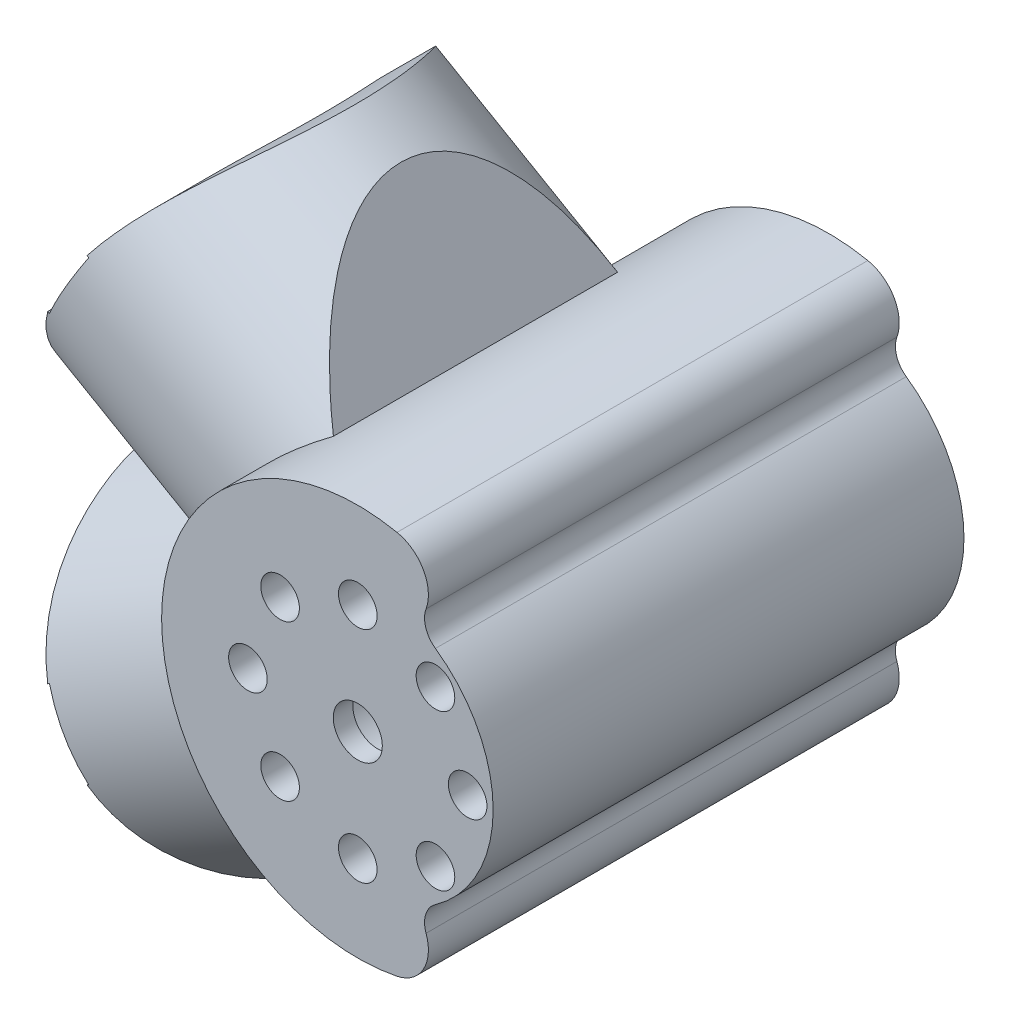
SolidWorks part; units mm, degrees
ref_plane "Front Plane" through (0, 0, 0) normal (0, 0, 1) x (1, 0, 0)
ref_plane "Top Plane" through (0, 0, 0) normal (0, 1, 0) x (1, 0, 0)
ref_plane "Right Plane" through (0, 0, 0) normal (1, 0, 0) x (0, 0, -1)
sketch "Sketch1" plane through (0, 0, 0) normal (0, 1, 0) x (1, 0, 0)
  circle A0 centre (0, 0) radius 11.176
  circle A1 centre (0, 0) radius 8.636
  dimension "D1" = 22.352
  dimension "D2" = 17.272
extrude "Boss-Extrude1" add sketch "Sketch1" along normal blind 20.32
sketch "Sketch2" plane through (0, 0, 0) normal (0, 0, 1) x (1, 0, 0)
  line L0 (11.176, 20.32) -> (-11.176, 20.32) construction
  line L1 (-8.636, 20.32) -> (-11.176, 20.32)
  line L2 (8.4632, 20.32) -> (11.0032, 20.32)
  line L3 (0, 20.32) -> (0, 38.4954) construction
  arc A2 (8.4632, 20.32) -> (-8.636, 20.32) centre (-0.0864, 7.6039) ccw
  arc A3 (11.0032, 20.32) -> (-11.176, 20.32) centre (-0.0864, 7.6039) ccw
revolve "Revolve1" add sketch "Sketch2" angle 360 about L3 region at (-9.906, 20.5457, 0)
ref_plane "Plane1" through (0, 27.94, 0) normal (0, -1, 0) x (-1, 0, 0)
sketch "Sketch3" plane through (0, 27.94, 0) normal (0, -1, 0) x (-1, 0, 0)
  line L0 (0, 11.9871) -> (0, -12.3331)
pattern_circular "CirPattern1" count 6 over 360 about axis through (0, 27.94, -11.9871) along (0, 0, 1) of bodies 103
sketch "Sketch4" plane through (0, 0, 0) normal (0, 0, 1) x (1, 0, 0)
  circle A0 centre (0, 27.94) radius 12.7
  dimension "D1" = 25.4
extrude "Boss-Extrude2" add sketch "Sketch4" along normal blind 13.97 and the other way blind 16.51
sketch "Sketch5" plane through (0, 0, 13.97) normal (0, 0, 1) x (1, 0, 0)
  circle A0 centre (0, 27.94) radius 25.4
  circle A1 centre (0, 27.94) radius 34.3456
  dimension "D1" = 50.8
extrude "Cut-Extrude1" cut sketch "Sketch5" against normal through all
sketch "Sketch8" plane through (0, 0, 0) normal (0, 1, 0) x (1, 0, 0)
  circle A0 centre (0, 0) radius 8.636
extrude "Cut-Extrude2" cut sketch "Sketch8" along normal up to surface (15.24 mm away) up to face at (0.2598, 15.3358, 2.1433)
pattern_circular "CirPattern2" count 6 over 360 about axis through (0, 27.94, -16.51) along (0, 0, 1) of "Cut-Extrude2"
sketch "Sketch9" plane through (0, 0, -16.51) normal (0, 0, -1) x (-1, 0, 0)
  line L0 (-159.3608, -65.013) -> (-26.0275, -65.013) construction
  line L1 (-5.3001, 25.0893) -> (-5.3001, 24.6378)
  line L2 (-5.3001, 32.5511) -> (5.1143, 32.5511)
  line L3 (-6.5701, 31.2811) -> (-6.5701, 23.7722)
  line L4 (-5.3001, 22.5022) -> (5.1143, 22.5022)
  line L5 (6.3843, 31.2811) -> (6.3843, 23.7722)
  line L6 (-4.9342, 31.6555) -> (4.7922, 31.6555)
  line L7 (-5.6962, 30.8935) -> (-5.6962, 24.1162)
  line L8 (-4.9342, 23.3542) -> (4.7922, 23.3542)
  line L9 (5.5542, 30.8935) -> (5.5542, 24.1162)
  line L10 (-5.3001, 24.6378) -> (-3.6843, 24.6378)
  line L11 (-3.6843, 24.6378) -> (-3.6843, 25.0893)
  line L12 (-3.6843, 25.0893) -> (-4.0153, 25.0893)
  line L13 (-4.0153, 25.0893) -> (-2.7662, 29.1074)
  line L14 (-2.7662, 29.1074) -> (-0.7496, 27.3015)
  line L15 (-0.7496, 27.3015) -> (-0.7496, 24.8635)
  line L16 (-0.7496, 24.8635) -> (-1.5021, 24.8635)
  line L17 (-1.5021, 24.8635) -> (-1.5021, 24.4572)
  line L18 (-1.5021, 24.4572) -> (-0.2379, 24.4572)
  line L19 (-0.2379, 24.4572) -> (-0.2379, 31.2811)
  line L20 (-0.2379, 31.2811) -> (-1.7579, 31.2811)
  line L21 (-1.7579, 31.2811) -> (-1.7579, 30.7478)
  line L22 (-1.7579, 30.7478) -> (-0.7496, 30.7478)
  line L23 (-0.7496, 30.7478) -> (-0.7496, 28.656)
  line L24 (-0.7496, 28.656) -> (-2.6007, 30.507)
  line L25 (-2.6007, 30.507) -> (-4.3163, 25.0893)
  line L26 (-4.3163, 25.0893) -> (-5.3001, 25.0893)
  line L27 (-0.071, 31.6555) -> (-0.071, 23.3542) construction
  line L28 (2.4587, 30.507) -> (4.1743, 25.0893)
  line L29 (0.6076, 28.656) -> (2.4587, 30.507)
  line L30 (0.6076, 30.7478) -> (0.6076, 28.656)
  line L31 (1.6159, 30.7478) -> (0.6076, 30.7478)
  line L32 (1.6159, 31.2811) -> (1.6159, 30.7478)
  line L33 (0.0959, 31.2811) -> (1.6159, 31.2811)
  line L34 (0.0959, 24.4572) -> (0.0959, 31.2811)
  line L35 (1.3601, 24.4572) -> (0.0959, 24.4572)
  line L36 (1.3601, 24.8635) -> (1.3601, 24.4572)
  line L37 (0.6076, 24.8635) -> (1.3601, 24.8635)
  line L38 (0.6076, 27.3015) -> (0.6076, 24.8635)
  line L39 (2.6242, 29.1074) -> (0.6076, 27.3015)
  line L40 (3.8733, 25.0893) -> (2.6242, 29.1074)
  line L41 (3.5422, 25.0893) -> (3.8733, 25.0893)
  line L42 (3.5422, 24.6378) -> (3.5422, 25.0893)
  line L43 (5.158, 24.6378) -> (3.5422, 24.6378)
  line L44 (5.158, 25.0893) -> (5.158, 24.6378)
  line L45 (4.1743, 25.0893) -> (5.158, 25.0893)
  line L47 (-5.3001, 24.3067) -> (5.1143, 24.3067)
  line L48 (-5.3001, 24.3067) -> (-5.3001, 23.8703)
  line L49 (-5.3001, 23.8703) -> (5.1143, 23.8703)
  line L50 (5.1143, 24.3067) -> (5.1143, 23.8703)
  arc A0 (5.1143, 32.5511) -> (6.3843, 31.2811) centre (5.1143, 31.2811) cw
  arc A1 (5.1143, 22.5022) -> (6.3843, 23.7722) centre (5.1143, 23.7722) ccw
  arc A2 (-6.5701, 23.7722) -> (-5.3001, 22.5022) centre (-5.3001, 23.7722) ccw
  arc A3 (-5.3001, 32.5511) -> (-6.5701, 31.2811) centre (-5.3001, 31.2811) ccw
  arc A4 (4.7922, 31.6555) -> (5.5542, 30.8935) centre (4.7922, 30.8935) cw
  arc A5 (4.7922, 23.3542) -> (5.5542, 24.1162) centre (4.7922, 24.1162) ccw
  arc A6 (-5.6962, 24.1162) -> (-4.9342, 23.3542) centre (-4.9342, 24.1162) ccw
  arc A7 (-4.9342, 31.6555) -> (-5.6962, 30.8935) centre (-4.9342, 30.8935) ccw
  dimension "D1" = 1.27
  dimension "D2" = 0.762
extrude "Cut-Extrude3" [suppressed] cut sketch "Sketch9" against normal blind 1.27 contours L25 L26 L1 L10 L11 L12 L13 L14 L15 L16 L17 L18 L19 L20 L21 L22 L23 L24 | L45 L28 L29 L30 L31 L32 L33 L34 L35 L36 L37 L38 L39 L40 L41 L42 L43 L44 | L2 A3 L3 A2 L4 A1 L5 A0 A7 L6 A4 L9 A5 L8 A6 L7
sketch "Sketch10" plane through (0, 0, 13.97) normal (0, 0, 1) x (1, 0, 0)
  circle A0 centre (0, 27.94) radius 1.5875
  arc A1 (-6.35, 38.9385) -> (-12.7, 27.94) centre (0, 27.94) ccw construction
  dimension "D1" = 3.175
extrude "Cut-Extrude4" cut sketch "Sketch10" against normal blind 1.27 contours A0
sketch "Sketch12" plane through (0, 0, 0) normal (0, 0, 1) x (1, 0, 0)
  line L1 (-12.7, 27.94) -> (-17.272, 27.94) construction
  arc A2 (-6.35, 38.9385) -> (-12.7, 27.94) centre (0, 27.94) ccw construction
  ellipse E0 centre (-12.7, 27.94) end of major axis (-17.78, 27.94) minor radius 1.27
  dimension "D1" = 10.16
  dimension "D2" = 2.54
extrude "Boss-Extrude3" add sketch "Sketch12" along normal up to next and the other way up to next
pattern_circular "CirPattern3" count 6 over 360 about axis through (0, 27.94, -16.51) along (0, 0, 1) of "Boss-Extrude3"
sketch "Sketch13" plane through (0, 0, -16.51) normal (0, 0, -1) x (-1, 0, 0)
  circle A0 centre (0, 27.94) radius 3.175
  circle A1 centre (0, 27.94) radius 12.7 construction
  dimension "D1" = 6.35
extrude "Cut-Extrude5" cut sketch "Sketch13" against normal up to surface (29.21 mm away) up to face at (1.5875, 27.94, 12.7)
sketch "Sketch14" plane through (0, 0, 13.97) normal (0, 0, 1) x (1, 0, 0)
  line L0 (-7.112, 27.94) -> (7.112, 27.94) construction
  circle A0 centre (-7.112, 27.94) radius 1.25
  point P5 (0, 27.94)
  dimension "D1" = 2.5
  dimension "D2" = 7.112
extrude "Cut-Extrude6" cut sketch "Sketch14" against normal blind 7
pattern_circular "CirPattern4" count 8 over 360 about axis through (0, 27.94, 13.97) along (0, 0, 1) of "Cut-Extrude6"
sketch "Sketch15" plane through (0, 0, 13.97) normal (0, 0, 1) x (1, 0, 0)
  line L1 (-2.54, 56.7733) -> (2.54, 56.7733)
  line L2 (-2.54, 56.7733) -> (-2.54, 53.086)
  line L3 (-2.54, 53.086) -> (2.54, 53.086)
  line L4 (2.54, 56.7733) -> (2.54, 53.086)
  arc A0 (8.636, 51.8268) -> (-8.636, 51.8268) centre (0, 27.94) ccw construction
  point P4 (0, 53.34)
  point P5 (0, 56.7733)
  dimension "D1" = 0.254
  dimension "D2" = 5.08
extrude "Cut-Extrude7" cut sketch "Sketch15" against normal through all
pattern_circular "CirPattern5" count 6 over 360 about axis through (0, 27.94, 13.97) along (0, 0, 1) of "Cut-Extrude7"
sketch "Sketch16" plane through (0, 0, -16.51) normal (0, 0, -1) x (-1, 0, 0)
  line L0 (11.176, 47.2974) -> (6.35, 38.9385)
  line L1 (11.176, 47.2974) -> (13.0675, 50.5735)
  line L2 (6.35, 16.9415) -> (13.0675, 5.3065)
  arc A0 (6.35, 38.9385) -> (6.35, 16.9415) centre (0, 27.94) ccw
  arc A1 (13.0675, 50.5735) -> (13.0675, 5.3065) centre (0, 27.94) ccw
extrude "Cut-Extrude8" cut sketch "Sketch16" against normal through all
sketch "Sketch18" plane through (0, 0, 13.97) normal (0, 0, 1) x (1, 0, 0)
  line L0 (-12.7, 27.94) -> (-22.352, 27.94) construction
  line L1 (4.4878, 37.1912) -> (5.543, 39.3665)
  line L2 (4.4878, 18.6888) -> (5.543, 16.5135)
  line L3 (0, 27.94) -> (5.543, 39.3665) construction
  line L4 (0, 27.94) -> (5.543, 16.5135) construction
  arc A0 (4.4878, 37.1912) -> (5.0263, 35.1182) centre (5.9732, 36.4706) ccw
  arc A1 (5.0263, 20.7618) -> (4.4878, 18.6888) centre (5.9732, 19.4094) ccw
  arc A2 (-12.7, 27.94) -> (-6.35, 16.9415) centre (0, 27.94) ccw construction
  circle A3 centre (0, 27.94) radius 12.7 construction
  arc A4 (5.0263, 20.7618) -> (5.0263, 35.1182) centre (0, 27.94) ccw
  arc A6 (5.543, 16.5135) -> (5.543, 39.3665) centre (0, 27.94) ccw
  point P4 (0, 27.94)
  point P5 (-12.7, 27.94)
  dimension "D2" = 3.302
  dimension "D1" = 10.414
  dimension "D3" = 10.414
  dimension "D4" = 110
  dimension "D5" = 125
extrude "Cut-Extrude9" cut sketch "Sketch18" against normal through all contours A0 A4 A1 L2 A6 L1
fillet "Fillet1" radius 2.54 2 edges at (5.543, 16.5135, -1.27) (5.543, 39.3665, -1.27)
